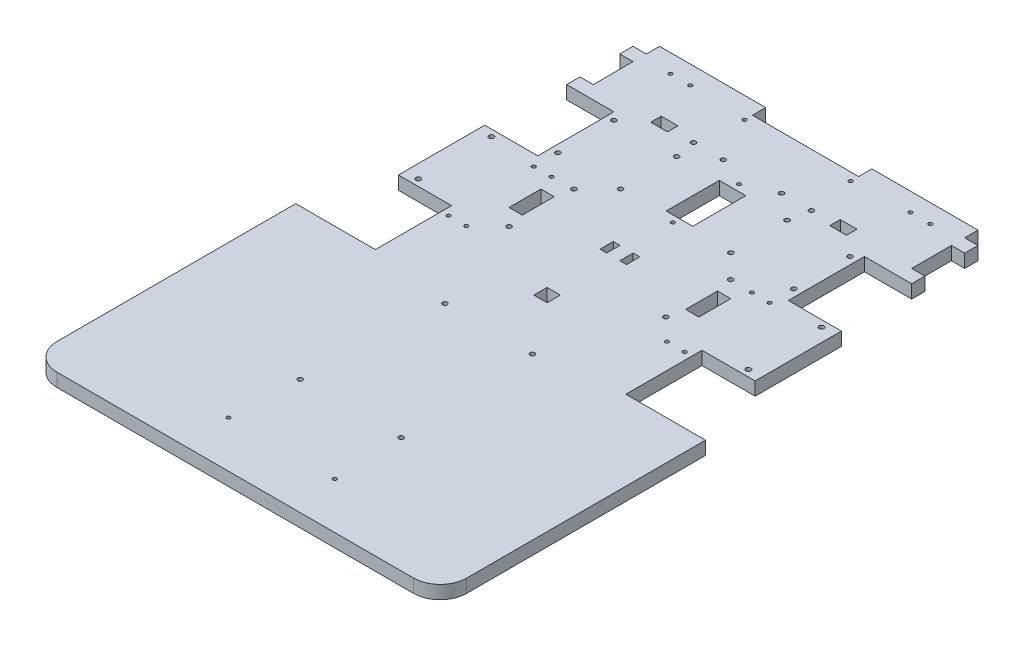
SolidWorks part; units mm, degrees
ref_plane "Front Plane" through (0, 0, 0) normal (0, 0, 1) x (1, 0, 0)
ref_plane "Top Plane" through (0, 0, 0) normal (0, 1, 0) x (1, 0, 0)
ref_plane "Right Plane" through (0, 0, 0) normal (1, 0, 0) x (0, 0, -1)
sketch "Sketch1" plane through (0, 0, 0) normal (0, 1, 0) x (1, 0, 0)
  line L0 (-147.6422, 18.3147) -> (-147.6422, -22.9603)
  line L1 (-138.4922, 92.8637) -> (-87.6922, 92.8637)
  line L2 (-122.2422, 54.7637) -> (-144.8422, 54.7637)
  line L3 (-62.2922, 26.1887) -> (-62.2922, 23.9027)
  line L4 (-62.2922, -186.4093) -> (-147.6422, -186.4093)
  line L5 (-144.8422, 54.7637) -> (-144.8422, 61.1137)
  line L6 (-144.8422, 80.1637) -> (-144.8422, 86.5137)
  line L7 (-147.6422, 18.3147) -> (-122.2422, 18.3147)
  line L8 (-122.2422, 54.7637) -> (-122.2422, 18.3147)
  line L9 (-147.6422, -22.9603) -> (-122.2422, -22.9603)
  line L10 (-107.7247, -9.9428) -> (-101.3747, -9.9428)
  line L11 (-160.3422, -173.7093) -> (-160.3422, -72.1093)
  line L12 (-122.2422, -22.9603) -> (-122.2422, -59.4093)
  line L13 (-147.6422, -59.4093) -> (-122.2422, -59.4093)
  line L14 (-107.7247, -9.9428) -> (-107.7247, 5.2972)
  line L15 (-107.7247, 5.2972) -> (-101.3747, 5.2972)
  line L16 (-101.3747, -9.9428) -> (-101.3747, 5.2972)
  line L17 (-107.7247, -9.9428) -> (-101.3747, 5.2972) construction
  line L18 (-107.7247, 5.2972) -> (-101.3747, -9.9428) construction
  line L19 (-160.3422, -72.1093) -> (-160.3422, -59.4093)
  line L20 (-160.3422, -59.4093) -> (-147.6422, -59.4093)
  line L21 (-144.8422, 86.5137) -> (-138.4922, 86.5137)
  line L22 (-138.4922, 92.8637) -> (-138.4922, 86.5137)
  line L23 (-144.8422, 80.1637) -> (-138.4922, 80.1637)
  line L24 (-62.2922, 51.5887) -> (-68.6422, 51.5887)
  line L25 (-144.8422, 61.1137) -> (-138.4922, 61.1137)
  line L26 (-138.4922, 80.1637) -> (-138.4922, 61.1137)
  line L27 (-62.2922, 86.5137) -> (-87.6922, 86.5137)
  line L28 (-87.6922, 92.8637) -> (-87.6922, 86.5137)
  line L29 (-62.2922, 86.5137) -> (-62.2922, 55.6527)
  line L30 (-62.2922, 22.1247) -> (-62.2922, -34.0093)
  line L31 (-62.2922, 26.1887) -> (-68.6422, 26.1887)
  line L32 (-68.6422, 51.5887) -> (-68.6422, 26.1887)
  line L33 (-62.2922, 53.8747) -> (-62.2922, 51.5887)
  line L34 (-62.2922, -40.3593) -> (-62.2922, -186.4093)
  line L35 (-68.6422, -5.4978) -> (-65.4672, -5.4978)
  line L36 (-68.6422, -5.4978) -> (-68.6422, 0.8522)
  line L37 (-109.1422, 64.2887) -> (-101.1422, 64.2887)
  line L38 (-109.1422, 64.2887) -> (-109.1422, 59.2887)
  line L39 (-109.1422, 59.2887) -> (-101.1422, 59.2887)
  line L40 (-101.1422, 64.2887) -> (-101.1422, 59.2887)
  line L41 (-68.6422, 0.8522) -> (-65.4672, 0.8522)
  line L42 (-65.4672, -5.4978) -> (-65.4672, 0.8522)
  line L43 (-68.6422, -5.4978) -> (-65.4672, 0.8522) construction
  line L44 (-68.6422, 0.8522) -> (-65.4672, -5.4978) construction
  line L45 (-62.2922, -40.3593) -> (-65.4672, -40.3593)
  line L47 (-62.2922, -34.0093) -> (-65.4672, -34.0093)
  line L48 (-65.4672, -40.3593) -> (-65.4672, -34.0093)
  circle A0 centre (-118.7497, -27.8153) radius 0.889
  circle A1 centre (-118.7497, 12.9197) radius 0.889
  circle A2 centre (-110.2647, 12.9197) radius 0.889
  circle A3 centre (-110.2647, -27.8153) radius 0.889
  circle A4 centre (-118.7497, 51.2712) radius 1.1303
  circle A5 centre (-118.7497, 24.398) radius 1.1303
  circle A6 centre (-88.7015, 51.2712) radius 1.1303
  circle A7 centre (-88.7015, 24.398) radius 1.1303
  circle A8 centre (-99.7922, 13.1772) radius 1.1303
  circle A9 centre (-99.7922, -17.8228) radius 1.1303
  circle A10 centre (-83.2472, -65.1243) radius 1.1303
  circle A11 centre (-86.4222, -131.1643) radius 1.1303
  arc A12 (-147.6422, -186.4093) -> (-160.3422, -173.7093) centre (-147.6422, -173.7093) cw
  circle A13 centre (-87.6922, -164.1843) radius 0.889
  circle A14 centre (-124.4972, 84.0487) radius 0.889
  circle A15 centre (-87.6922, 82.7037) radius 0.889
  circle A16 centre (-90.4922, 61.1137) radius 1.1303
  circle A17 centre (-76.2047, 61.1137) radius 1.1303
  arc A18 (-62.2922, 55.6527) -> (-62.2922, 53.8747) centre (-62.2922, 54.7637) ccw
  arc A19 (-62.2922, 23.9027) -> (-62.2922, 22.1247) centre (-62.2922, 23.0137) ccw
  circle A20 centre (-114.9722, 84.0487) radius 0.889
  point P14 (-104.5497, -2.3228)
  point P49 (-160.3422, -186.4093)
  point P52 (-160.3422, -59.4093)
  point P74 (-67.0547, -2.3228)
  dimension "D9" = 1.778
  dimension "D10" = 1.778
  dimension "D11" = 3.4925
  dimension "D12" = 3.4925
  dimension "D14" = 4.855
  dimension "D21" = 3.4925
  dimension "D22" = 3.4925
  dimension "D23" = 26.8732
  dimension "D24" = 30.0482
  dimension "D25" = 2.2606
  dimension "D26" = 2.2606
  dimension "D27" = 2.2606
  dimension "D28" = 2.2606
  dimension "D35" = 2.2606
  dimension "D36" = 2.2606
  dimension "D37" = 31
  dimension "D38" = 15.5
  dimension "D39" = 2.2606
  dimension "D41" = 2.2606
  dimension "D42" = 14.2875
  dimension "D43" = 2.2606
  dimension "D44" = 66.04
  dimension "D45" = 6.35
  dimension "D46" = 12.7
  dimension "D52" = 22.225
  dimension "D53" = 6.35
  dimension "D54" = 1.778
  dimension "D56" = 27.28
  dimension "D57" = 9.525
  dimension "D59" = 0
  dimension "D60" = 3.81
  dimension "D63" = 26.8732
  dimension "D66" = 1.778
  dimension "D8" = 2.2606
  dimension "D49" = 31.75
  dimension "D61" = 3.175
  dimension "D62" = 1.778
  dimension "D64" = 3.175
  dimension "D65" = 1.778
  dimension "D58" = 1.345
  dimension "D68" = 1.778
  dimension "D77" = 1.778
  dimension "D1" = 41.275
  dimension "D2" = 25.4
  dimension "D3" = 25.4
  dimension "D4" = 36.449
  dimension "D5" = 36.449
  dimension "D6" = 22.6
  dimension "D7" = 38.1
  dimension "D13" = 5.395
  dimension "D16" = 2.54
  dimension "D17" = 15.24
  dimension "D18" = 20.6375
  dimension "D19" = 6.35
  dimension "D20" = 127
  dimension "D29" = 6.35
  dimension "D30" = 6.35
  dimension "D31" = 6.35
  dimension "D32" = 6.35
  dimension "D33" = 6.35
  dimension "D34" = 0
  dimension "D40" = 5.715
  dimension "D47" = 6.35
  dimension "D48" = 25.4
  dimension "D50" = 3.175
  dimension "D51" = 25.4
  dimension "D55" = 50.8
  dimension "D67" = 8
  dimension "D69" = 5
  dimension "D70" = 3.175
  dimension "D71" = 6.35
  dimension "D72" = 3.175
  dimension "D73" = 0
  dimension "D74" = 6.35
  dimension "D75" = 3.175
  dimension "D76" = 19.05
  dimension "D15" = 2
extrude "Boss-Extrude1" add sketch "Sketch1" along normal blind 6.35
sketch "Sketch2" plane through (0, 6.35, 0) normal (0, 1, 0) x (1, 0, 0)
  line L0 (-147.6422, 18.3147) -> (-147.6422, -22.9603) construction
  circle A0 centre (-141.2922, 15.1772) radius 1.1684
  circle A1 centre (-141.2922, -19.8228) radius 1.1684
  point P6 (-147.6422, -2.3228)
  point P7 (-147.6422, -2.3228)
  dimension "D1" = 2.3368
  dimension "D2" = 2.3368
  dimension "D3" = 6.35
  dimension "D4" = 6.35
  dimension "D5" = 17.5
  dimension "D6" = 17.5
extrude "Cut-Extrude1" cut sketch "Sketch2" against normal blind 6.35
mirror "Mirror1" about plane through (-62.2922, 6.35, -86.5137) normal (-1, 0, 0) of "Boss-Extrude1", "Cut-Extrude1"
